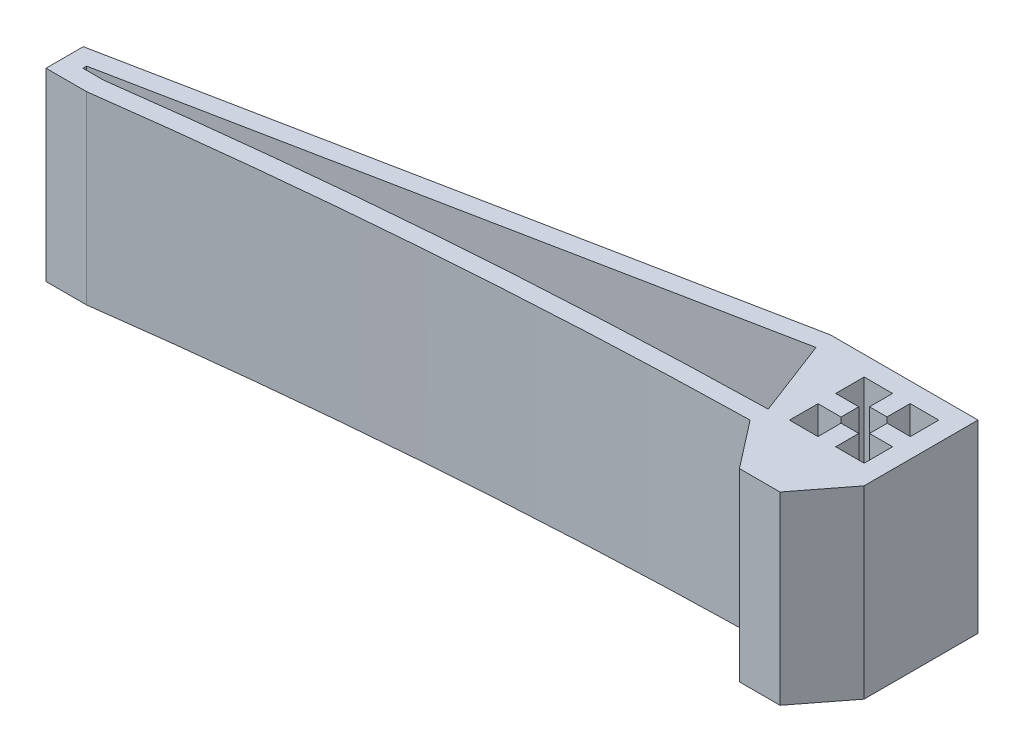
SolidWorks part; units mm, degrees
ref_plane "Plan de face" through (0, 0, 0) normal (0, 0, 1) x (1, 0, 0)
ref_plane "Plan de dessus" through (0, 0, 0) normal (0, 1, 0) x (1, 0, 0)
ref_plane "Plan de droite" through (0, 0, 0) normal (1, 0, 0) x (0, 0, -1)
sketch "Esquisse1" plane through (0, 0, 0) normal (0, 1, 0) x (1, 0, 0)
  line L0 (-15.4191, 0) -> (15.4191, 0) construction
  line L7 (0, 15.4191) -> (0, -15.4191) construction
  line L8 (-9.8036, -9.8036) -> (10.1964, 10.1964) construction
  line L9 (-9.8036, -2.3036) -> (-9.8036, -9.8036) construction
  line L10 (-9.8036, -2.3036) -> (-8.4647, -2.3036) construction
  line L11 (-8.4647, -2.3036) -> (-8.4647, -6.0358) construction
  line L12 (-7.6111, -6.3893) -> (-3.7147, -2.4929) construction
  line L13 (-6.5505, -7.45) -> (-2.654, -3.5536) construction
  line L14 (-2.4647, -8.3036) -> (-6.1969, -8.3036) construction
  line L15 (-2.4647, -9.8036) -> (-2.4647, -8.3036) construction
  line L16 (-2.4647, -9.8036) -> (-9.8036, -9.8036) construction
  line L17 (-2.5353, 10.1964) -> (-2.5353, 8.6964) construction
  line L18 (-2.5353, 10.1964) -> (-10.0353, 10.1964) construction
  line L19 (-10.0353, 2.6964) -> (-10.0353, 10.1964) construction
  line L20 (-10.0353, 2.6964) -> (-8.4647, 2.6964) construction
  line L21 (-8.4647, 2.6964) -> (-8.4647, 6.4287) construction
  line L22 (-7.6111, 6.7822) -> (-3.7147, 2.8858) construction
  line L23 (-6.6211, 7.8429) -> (-2.7247, 3.9464) construction
  line L24 (-2.5353, 8.6964) -> (-6.2676, 8.6964) construction
  line L25 (10.0353, 2.6964) -> (8.5353, 2.6964) construction
  line L26 (10.0353, 2.6964) -> (10.1964, 10.1964) construction
  line L27 (2.5353, 10.1964) -> (10.1964, 10.1964) construction
  line L28 (2.5353, 10.1964) -> (2.5353, 8.6964) construction
  line L29 (2.5353, 8.6964) -> (6.2676, 8.6964) construction
  line L30 (6.6211, 7.8429) -> (2.7247, 3.9464) construction
  line L31 (7.6818, 6.7822) -> (3.7853, 2.8858) construction
  line L32 (8.5353, 2.6964) -> (8.5353, 6.4287) construction
  line L33 (2.4647, -9.8036) -> (2.4647, -8.3036) construction
  line L34 (2.4647, -9.8036) -> (10.1964, -9.8036) construction
  line L35 (10.0353, -2.3036) -> (10.1964, -9.8036) construction
  line L36 (10.0353, -2.3036) -> (8.5353, -2.3036) construction
  line L37 (8.5353, -2.3036) -> (8.5353, -6.0358) construction
  line L38 (7.6818, -6.3893) -> (3.7853, -2.4929) construction
  line L39 (6.6211, -7.45) -> (2.7247, -3.5536) construction
  line L40 (2.4647, -8.3036) -> (6.2676, -8.3036) construction
  line L41 (-3.7147, 2.8858) -> (-3.7147, -2.4929) construction
  line L42 (-2.654, -3.5536) -> (2.7247, -3.5536) construction
  line L43 (-2.7247, 3.9464) -> (2.7247, 3.9464) construction
  line L44 (3.7853, 2.8858) -> (3.7853, -2.4929) construction
  line L63 (-10.0736, 10.1) -> (-2.3736, 10.1)
  line L65 (15.4191, -15.4191) -> (15.4191, 15.4191)
  line L66 (15.4191, 15.4191) -> (-15.4191, 15.4191)
  line L68 (15.4191, -15.4191) -> (-15.4191, 15.4191) construction
  line L69 (15.4191, 15.4191) -> (-15.4191, -15.4191) construction
  line L70 (-2.3736, 10.1) -> (-2.3736, 3.85)
  line L71 (-2.3736, 3.85) -> (2.3736, 3.85)
  line L72 (2.3736, 3.85) -> (2.3736, 10.1)
  line L73 (2.3736, 10.1) -> (10.1264, 10.1)
  line L74 (10.1264, 10.1) -> (10.1264, 2.4)
  line L75 (10.1264, 2.4) -> (3.8764, 2.4)
  line L76 (3.8764, -2.4) -> (3.8764, 2.4)
  line L77 (10.1264, -2.4) -> (3.8764, -2.4)
  line L78 (10.1264, -10.1) -> (10.1264, -2.4)
  line L79 (2.4264, -10.1) -> (10.1264, -10.1)
  line L80 (2.4264, -3.85) -> (2.4264, -10.1)
  line L81 (-2.3736, -3.85) -> (2.4264, -3.85)
  line L82 (-2.3736, -10.1) -> (-2.3736, -3.85)
  line L83 (-10.0736, -10.1) -> (-2.3736, -10.1)
  line L84 (-10.0736, -2.4) -> (-10.0736, -10.1)
  line L85 (-3.8236, -2.4) -> (-10.0736, -2.4)
  line L86 (-3.8236, 2.4) -> (-3.8236, -2.4)
  line L87 (-10.0736, 2.4) -> (-3.8236, 2.4)
  line L88 (-10.0736, 2.4) -> (-10.0736, 10.1)
  line L90 (-182.1851, -28.2346) -> (-193.1602, -28.2346)
  line L94 (-5.4875, -28.2346) -> (5.4875, -28.2346)
  line L95 (5.4875, -28.2346) -> (15.4191, -15.4191)
  line L96 (-5.4875, -28.2346) -> (-15.4191, -15.4191)
  line L97 (-193.1602, -28.2346) -> (-193.1602, -18.1382)
  line L99 (-15.4191, 15.4191) -> (-24.4944, 15.4191)
  line L100 (-24.4944, 15.4191) -> (-193.1602, -18.1382)
  line L101 (-23.5188, 10.5152) -> (-188.1602, -22.2414)
  line L102 (-188.1602, -23.2346) -> (-188.1602, -22.2414)
  line L103 (-182.5189, -23.2346) -> (-188.1602, -23.2346)
  line L104 (-15.5187, -10.4201) -> (-23.5188, 10.5152)
  arc A0 (-8.4647, 6.4287) -> (-7.6111, 6.7822) centre (-7.9647, 6.4287) cw construction
  arc A1 (-8.4647, -6.0358) -> (-7.6111, -6.3893) centre (-7.9647, -6.0358) ccw construction
  arc A2 (-6.5505, -7.45) -> (-6.1969, -8.3036) centre (-6.1969, -7.8036) ccw construction
  arc A3 (6.6211, -7.45) -> (6.2676, -8.3036) centre (6.2676, -7.8036) cw construction
  arc A4 (8.5353, -6.0358) -> (7.6818, -6.3893) centre (8.0353, -6.0358) cw construction
  arc A5 (7.6818, 6.7822) -> (8.5353, 6.4287) centre (8.0353, 6.4287) cw construction
  arc A6 (6.2676, 8.6964) -> (6.6211, 7.8429) centre (6.2676, 8.1964) cw construction
  arc A7 (-6.6211, 7.8429) -> (-6.2676, 8.6964) centre (-6.2676, 8.1964) cw construction
  spline S0 degree 2 poles (-182.1851, -28.2346) (-99.136, -17.0866) (-15.4191, -15.4191) knots 0 0 0 1 1 1
  spline S1 degree 1 poles (-182.5189, -23.2346) (-15.5187, -10.4201) knots 0 0 1 1 construction
  spline S2 degree 2 poles (-182.5189, -23.2346) (-99.3528, -12.0899) (-15.5187, -10.4201) knots 0.001988 0.001988 0.001988 1 1 1
  point P1 (-3.8236, 0)
  point P2 (0, 3.85)
  point P11 (-2.4647, -9.0536)
  point P12 (2.4647, -9.0536)
  point P54 (0, 0)
  point P67 (0, 0)
  point P93 (0, -28.2346)
  dimension "D8" = 0.5
  dimension "D1" = 5
  dimension "D3" = 20
  dimension "D5" = 7.5
  dimension "D6" = 1.5
  dimension "D7" = 1.5
extrude "Boss.-Extru.1" add sketch "Esquisse1" along normal blind 50
